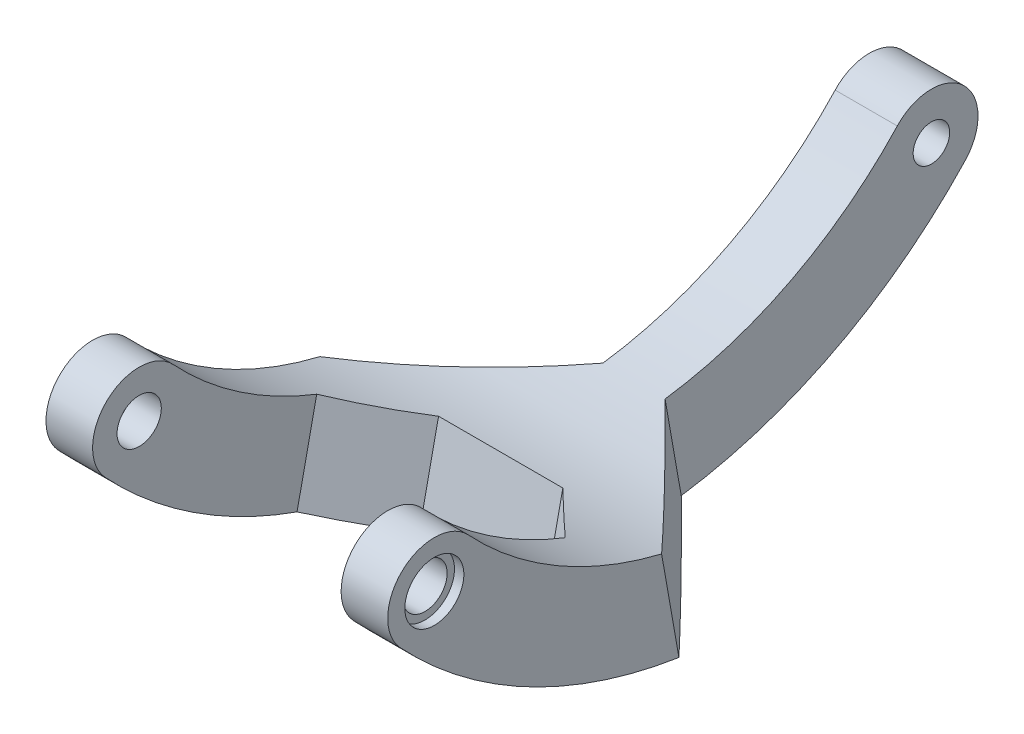
SolidWorks part; units mm, degrees
material "环氧树脂,未充填"
ref_plane "前视基准面" through (0, 0, 0) normal (0, 0, 1) x (1, 0, 0)
ref_plane "上视基准面" through (0, 0, 0) normal (0, 1, 0) x (1, 0, 0)
ref_plane "右视基准面" through (0, 0, 0) normal (1, 0, 0) x (0, 0, -1)
other "Configuration Table"
sketch "草图1" plane through (0, 0, 0) normal (1, 0, 0) x (0, 0, -1)
  line L0 (-20.5, 0) -> (20.5, 0) construction
  line L1 (-20.5, 0) -> (20.5, 0) construction
  line L2 (-20.5, 3) -> (20.5, 3) construction
  line L3 (-20.5, -3) -> (20.5, -3) construction
  line L4 (0, 19.0722) -> (-6.4804, -11.2429) construction
  line L5 (-20.5, 0) -> (0, 19.0722) construction
  line L6 (-6.4804, -11.2429) -> (-5.2261, -5.3754)
  line L7 (0, 19.0722) -> (14.1057, -8.5327) construction
  line L8 (14.1057, -8.5327) -> (11.3755, -3.1898)
  line L9 (20.5, 0) -> (0, 19.0722) construction
  circle A0 centre (20.5, 0) radius 1.175
  circle A1 centre (-20.5, 0) radius 1.425
  arc A2 (-20.5, 3) -> (-20.5, -3) centre (-20.5, 0) ccw construction
  arc A3 (20.5, -3) -> (20.5, 3) centre (20.5, 0) ccw construction
  arc A4 (-20.5, 0) -> (20.5, 0) centre (0, 19.0722) ccw construction
  arc A9 (-22.6964, -2.0435) -> (22.6964, -2.0435) centre (0, 19.0722) ccw
  arc A10 (-18.3036, 2.0435) -> (18.3036, 2.0435) centre (0, 19.0722) ccw
  arc A11 (-18.3036, 2.0435) -> (-22.6964, -2.0435) centre (-20.5, 0) ccw
  arc A12 (22.6964, -2.0435) -> (18.3036, 2.0435) centre (20.5, 0) ccw
  point P4 (0, 0)
  point P8 (0, 0)
  point P15 (0, -8.9278)
  dimension "D1" = 2.35
  dimension "D3" = 3
  dimension "D4" = 3
  dimension "D5" = 25
  dimension "D6" = 2.85
  dimension "D2" = 41
  dimension "D7" = 35
  dimension "D8" = 20
extrude "凸台-拉伸1" add sketch "草图1" along normal mid plane 22 contours A10 A11 A9 L6 A1 | A9 A12 A10 L6 A0 | A10 L6 A9 L8 region at (0, -4.526, 14.2465) region at (0, -8.256, -3.5978) region at (0, -2.5851, -17.5564)
extrude "切除-拉伸1" cut sketch "草图1<6>" along normal offset from surface 3 and the other way offset from surface 3 contours A10 A11 A9 L6 A1 region at (0, -4.526, 14.2465) up to face at (11, 0, 19.075) other way up to face at (-11, 0, 19.075)
sketch "草图1<6>" plane through (0, 0, 0) normal (1, 0, 0) x (0, 0, -1) same geometry as "草图1"
sketch "草图4" plane through (11, 0, 0) normal (1, 0, 0) x (0, 0, -1)
  line L0 (0, 19.0722) -> (8682.4089, -49221.3154) construction
  line L1 (0, 0) -> (0, 50000) construction
  line L2 (0, 19.0722) -> (5.3831, -11.4568)
  line L3 (22.2964, 2.4027) -> (0, 19.0722)
  arc A0 (20.5, 0) -> (-20.5, 0) centre (0, 19.0722) cw construction
  arc A2 (22.6964, -2.0435) -> (18.3036, 2.0435) centre (20.5, 0) ccw construction
  arc A3 (22.6964, -2.0435) -> (18.3036, 2.0435) centre (20.5, 0) ccw
  arc A4 (-22.6964, -2.0435) -> (22.6964, -2.0435) centre (0, 19.0722) ccw construction
  arc A5 (-18.3036, 2.0435) -> (18.3036, 2.0435) centre (0, 19.0722) ccw construction
  arc A6 (-22.6964, -2.0435) -> (22.6964, -2.0435) centre (0, 19.0722) ccw
  arc A7 (-18.3036, 2.0435) -> (18.3036, 2.0435) centre (0, 19.0722) ccw construction
  arc M5 (18.3036, 2.0435) -> (-18.3036, 2.0435) centre (0, 19.0722) cw
  arc M7 (-22.6964, -2.0435) -> (22.6964, -2.0435) centre (0, 19.0722) ccw
  arc M8 (22.6964, -2.0435) -> (18.3036, 2.0435) centre (20.5, 0) ccw
  circle M9 centre (20.5, 0) radius 1.175
  dimension "D2" = 10
extrude "切除-拉伸3" cut sketch "草图4" against normal offset from surface (9 mm away) 2 contours L2 M5 M7 M8 M9 region at (11, -4.652, -13.9008) up to plane "右视基准面"
sketch "草图6" plane through (11, 0, 0) normal (1, 0, 0) x (0, 0, -1)
  circle A0 centre (-20.5, 0) radius 1.9
  dimension "D1" = 3.8
extrude "切除-拉伸5" cut sketch "草图6" against normal blind 0.6 and the other way through all
mirror "镜向3" about plane through (0, 0, 0) normal (1, 0, 0) of "切除-拉伸5", "切除-拉伸3"
sketch "草图3" plane through (-11, 0, 0) normal (-1, 0, 0) x (0, 0, 1)
  circle A0 centre (20.5, 0) radius 1.85
  dimension "D1" = 3.7
extrude "切除-拉伸2" cut sketch "草图3" against normal blind 1
sketch "草图5" plane through (2, 0, 0) normal (1, 0, 0) x (0, 0, -1)
  line L0 (20.5, 0) -> (0, 19.0722) construction
  line L1 (0, 19.0722) -> (18.7597, -1.7141) construction
  arc A0 (20.5, 0) -> (18.7597, -1.7141) centre (0, 19.0722) cw construction
  arc A1 (19.547, -2.5864) -> (21.3603, -0.8004) centre (0, 19.0722) ccw
  arc A2 (17.9725, -0.8418) -> (19.6397, 0.8004) centre (0, 19.0722) ccw
  arc A3 (17.9725, -0.8418) -> (19.547, -2.5864) centre (18.7597, -1.7141) ccw
  arc A4 (21.3603, -0.8004) -> (19.6397, 0.8004) centre (20.5, 0) ccw
  circle A5 centre (20.5, 0) radius 1.175 construction
  arc A6 (-18.3036, 2.0435) -> (4.3412, -5.548) centre (0, 19.0722) ccw construction
  point P4 (19.6486, -0.876)
  dimension "D1" = 5
extrude "切除-拉伸4" [suppressed] cut sketch "草图5" against normal through all both and the other way through all
chamfer "倒角2" distance 10 angle 45 2 edges at (-11, -8.5024, -4.8621) (11, -8.5024, -4.8621)
chamfer "倒角3" distance 4 angle 45 2 edges at (-8, -8.3091, 5.8532) (8, -8.3091, 5.8532)
